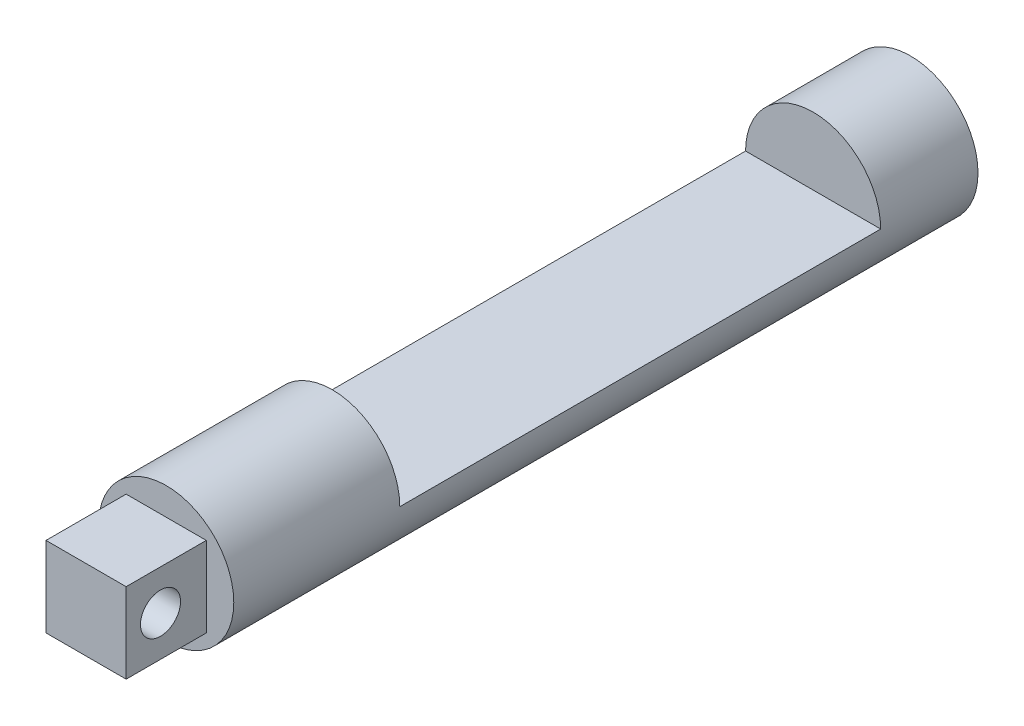
SolidWorks part; units mm, degrees
ref_plane "Alzado" through (0, 0, 0) normal (0, 0, 1) x (1, 0, 0)
ref_plane "Planta" through (0, 0, 0) normal (0, 1, 0) x (1, 0, 0)
ref_plane "Vista lateral" through (0, 0, 0) normal (1, 0, 0) x (0, 0, -1)
sketch "Croquis1" plane through (0, 0, 0) normal (0, 0, 1) x (1, 0, 0)
  circle A0 centre (0, 0) radius 5.9
  dimension "D1" = 11.8
extrude "Saliente-Extruir1" add sketch "Croquis1" along normal mid plane 65
sketch "Croquis2" plane through (0, 0, 0) normal (0, 0, 1) x (1, 0, 0)
  line L0 (-5.9, 0) -> (5.9, 0)
  circle A0 centre (0, 0) radius 5.9 construction
  arc A1 (5.9, 0) -> (-5.9, 0) centre (0, 0) ccw
extrude "Cortar-Extruir1" cut sketch "Croquis2" against normal blind 24
sketch "Croquis3" plane through (0, 0, 32.5) normal (0, 0, 1) x (1, 0, 0)
  circle A0 centre (0, 0) radius 5
  dimension "D1" = 10
extrude "Cortar-Extruir-Lámina1" cut sketch "Croquis3" against normal blind 3 from offset 6.5 thin offset against normal yes thin type one direction wall 0.8
sketch "Croquis4" plane through (0, 0, 32.5) normal (0, 0, 1) x (1, 0, 0)
  line L1 (-3.5, 3.5) -> (3.5, 3.5)
  line L2 (-3.5, 3.5) -> (-3.5, -3.5)
  line L3 (-3.5, -3.5) -> (3.5, -3.5)
  line L4 (3.5, 3.5) -> (3.5, -3.5)
  line L5 (-3.5, 3.5) -> (3.5, -3.5) construction
  line L6 (-3.5, -3.5) -> (3.5, 3.5) construction
  point P0 (0, 0)
  dimension "D1" = 7
  dimension "D2" = 7
extrude "Saliente-Extruir2" add sketch "Croquis4" along normal blind 7
sketch "Croquis6" plane through (-3.5, 0, 0) normal (-1, 0, 0) x (0, 0, 1)
  line L1 (0, 0) -> (36.5, 0) construction
  line L2 (32.5, 3.5) -> (32.5, -3.5) construction
  circle A0 centre (36.5, 0) radius 1.75
  dimension "D1" = 3.5
  dimension "D2" = 4
extrude "Cortar-Extruir3" cut sketch "Croquis6" against normal through all
extrude "Cortar-Extruir4" cut sketch "Croquis2<2>" along normal blind 18
sketch "Croquis2<2>" plane through (0, 0, 0) normal (0, 0, 1) x (1, 0, 0) same geometry as "Croquis2"
